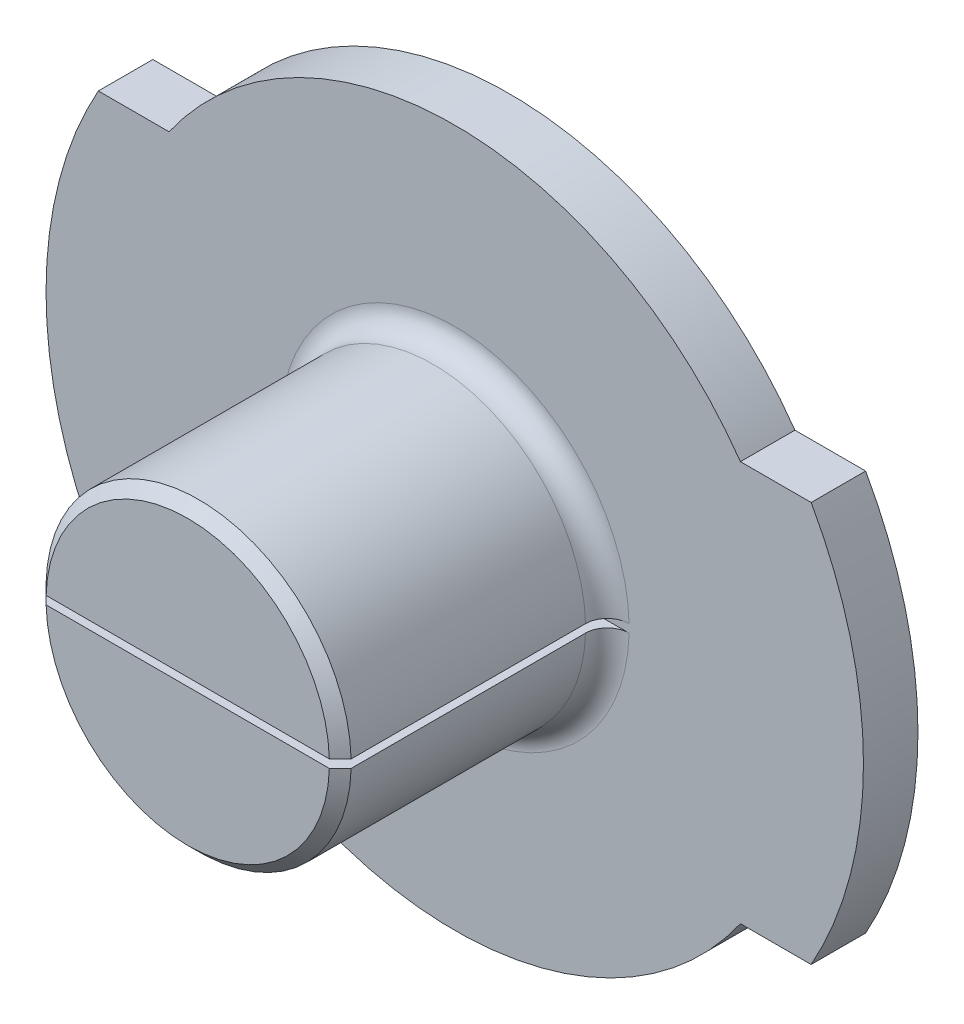
SolidWorks part; units mm, degrees
ref_plane "Front" through (0, 0, 0) normal (0, 0, 1) x (1, 0, 0)
ref_plane "Top" through (0, 0, 0) normal (0, 1, 0) x (1, 0, 0)
ref_plane "Right" through (0, 0, 0) normal (1, 0, 0) x (0, 0, -1)
sketch "Sketch1" plane through (0, 0, 0) normal (1, 0, 0) x (0, 0, -1)
  line L0 (0, 0) -> (0, 9.525)
  line L1 (0, 9.525) -> (-1.27, 9.525)
  line L2 (-1.27, 9.525) -> (-1.27, 3.556)
  line L3 (-1.27, 3.556) -> (-7.493, 3.556)
  line L4 (-7.493, 3.556) -> (-7.493, 0)
  line L5 (-7.493, 0) -> (0, 0)
  line L6 (0, 0) -> (14.0505, 0) construction
  dimension "D1" = 7.112
  dimension "D2" = 19.05
  dimension "D3" = 1.27
  dimension "D4" = 6.223
revolve "Revolve1" add sketch "Sketch1" angle 360 about L6
chamfer "Chamfer1" distance 0.254 angle 45 1 edges at (3.556, 0, 7.493)
fillet "Fillet2" radius 0.508 1 edges at (3.556, 0, 1.27)
sketch "Sketch2" plane through (0, 0, 7.493) normal (0, 0, 1) x (1, 0, 0)
  line L1 (-5.9582, -0.0952) -> (5.9582, -0.0952)
  line L2 (-5.9582, -0.0952) -> (-5.9582, 0.0953)
  line L3 (-5.9582, 0.0953) -> (5.9582, 0.0953)
  line L4 (5.9582, -0.0952) -> (5.9582, 0.0953)
  line L5 (-5.9582, -0.0952) -> (5.9582, 0.0953) construction
  line L6 (-5.9582, 0.0953) -> (5.9582, -0.0952) construction
  point P0 (0, 0)
  dimension "D1" = 0.1905
extrude "Cut-Extrude1" cut sketch "Sketch2" against normal up to surface (6.223 mm away) up to face at (-4.064, 0, 1.27)
fillet "Fillet1" radius 0.254 rebuild error yes
sketch "Sketch3" plane through (0, 0, 0) normal (0, 0, -1) x (-1, 0, 0)
  line L1 (-15.6514, -4.6625) -> (15.6514, -4.6625)
  line L2 (-15.6514, -4.6625) -> (-15.6514, 4.6625)
  line L3 (-15.6514, 4.6625) -> (15.6514, 4.6625)
  line L4 (15.6514, -4.6625) -> (15.6514, 4.6625)
  line L5 (-15.6514, -4.6625) -> (15.6514, 4.6625) construction
  line L6 (-15.6514, 4.6625) -> (15.6514, -4.6625) construction
  circle A0 centre (0, 0) radius 8.128
  point P0 (0, 0)
  point P6 (0, 0)
  circle M1 centre (0, 0) radius 9.525
  dimension "D2" = 16.256
  dimension "D1" = 9.325
extrude "Cut-Extrude2" cut sketch "Sketch3" against normal through all contours A0 L3 M1 | A0 L1 M1 region at (7.4818, -4.8356, 0) region at (0, 9.3519, 0)
